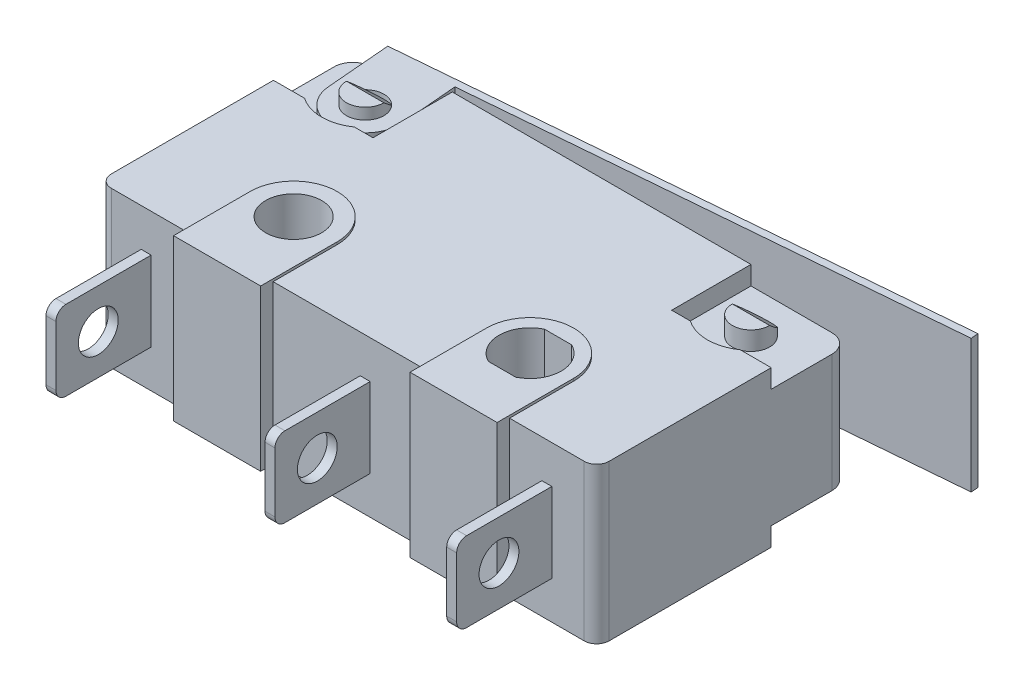
SolidWorks part; units mm, degrees
ref_plane "Front Plane" through (0, 0, 0) normal (0, 0, 1) x (1, 0, 0)
ref_plane "Top Plane" through (0, 0, 0) normal (0, 1, 0) x (1, 0, 0)
ref_plane "Right Plane" through (0, 0, 0) normal (1, 0, 0) x (0, 0, -1)
sketch "Sketch1" plane through (0, 0, 0) normal (0, 1, 0) x (1, 0, 0)
  line L1 (-10, -5.1) -> (10, -5.1)
  line L2 (-10, -5.1) -> (-10, 5.1)
  line L3 (-10, 5.1) -> (10, 5.1)
  line L4 (10, -5.1) -> (10, 5.1)
  line L5 (-10, -5.1) -> (10, 5.1) construction
  line L6 (-10, 5.1) -> (10, -5.1) construction
  point P0 (0, 0)
  dimension "D1" = 20
  dimension "D2" = 10.2
extrude "Boss-Extrude1" add sketch "Sketch1" along normal blind 6.25
fillet "Fillet1" radius 0.75 2 edges at (10, 3.125, -5.1) (-10, 3.125, -5.1)
fillet "Fillet2" radius 0.5 2 edges at (10, 3.125, 5.1) (-10, 3.125, 5.1)
sketch "Sketch2" plane through (0, 6.25, 0) normal (0, 1, 0) x (1, 0, 0)
  line L0 (5.2949, -1.4) -> (4.2051, -1.4)
  line L1 (4.2051, -3.65) -> (5.2949, -3.65)
  line L2 (4.75, -2.525) -> (4.75, -1.4) construction
  line L3 (4.75, -2.525) -> (4.75, -3.65) construction
  line L4 (0, -5.1) -> (0, -2.525) construction
  line L5 (-9.5, -5.1) -> (9.5, -5.1) construction
  line L6 (0, -2.525) -> (4.75, -2.525) construction
  line L7 (0, -2.525) -> (-4.75, -2.525) construction
  line L8 (-4.75, -1.4) -> (-4.75, 5.1) construction
  line L9 (9.25, 5.1) -> (-9.25, 5.1) construction
  line L10 (-4.75, -3.65) -> (-4.75, -5.1) construction
  circle A0 centre (-4.75, -2.525) radius 1.125
  arc A1 (4.2051, -1.4) -> (4.2051, -3.65) centre (4.75, -2.525) ccw
  arc A2 (5.2949, -3.65) -> (5.2949, -1.4) centre (4.75, -2.525) ccw
  dimension "D1" = 2.5
  dimension "D5" = 2.25
  dimension "D2" = 2.25
  dimension "D3" = 9.5
  dimension "D4" = 6.5
extrude "Cut-Extrude1" cut sketch "Sketch2" against normal through all
sketch "Sketch3" plane through (0, 6.25, 0) normal (0, 1, 0) x (1, 0, 0)
  line L0 (-6.5, -5.1) -> (-6.5, -2.525)
  line L1 (-9.5, -5.1) -> (9.5, -5.1) construction
  line L2 (-3, -2.525) -> (-3, -5.1)
  line L3 (-3, -5.1) -> (-3, -5.6)
  line L4 (-3, -5.6) -> (-6.5, -5.6)
  line L5 (-6.5, -5.6) -> (-6.5, -5.1)
  line L6 (0, -5.1) -> (0, 0) construction
  line L7 (6.5, -5.6) -> (6.5, -5.1)
  line L8 (3, -5.6) -> (6.5, -5.6)
  line L9 (3, -5.1) -> (3, -5.6)
  line L10 (3, -2.525) -> (3, -5.1)
  line L11 (6.5, -5.1) -> (6.5, -2.525)
  line L12 (4.2051, -3.65) -> (5.2949, -3.65) construction
  line L13 (5.2949, -1.4) -> (4.2051, -1.4) construction
  line L14 (4.2051, -3.65) -> (5.2949, -3.65)
  line L15 (5.2949, -1.4) -> (4.2051, -1.4)
  arc A0 (-3, -2.525) -> (-6.5, -2.525) centre (-4.75, -2.525) ccw
  circle A1 centre (-4.75, -2.525) radius 1.125 construction
  arc A2 (3, -2.525) -> (6.5, -2.525) centre (4.75, -2.525) cw
  arc A3 (5.2949, -3.65) -> (5.2949, -1.4) centre (4.75, -2.525) ccw construction
  arc A4 (4.2051, -1.4) -> (4.2051, -3.65) centre (4.75, -2.525) ccw construction
  arc A5 (5.2949, -3.65) -> (5.2949, -1.4) centre (4.75, -2.525) ccw
  arc A6 (4.2051, -1.4) -> (4.2051, -3.65) centre (4.75, -2.525) ccw
  circle A7 centre (-4.75, -2.525) radius 1.125
  dimension "D1" = 3.5
  dimension "D2" = 0.5
extrude "Boss-Extrude2" add sketch "Sketch3" against normal offset from surface (6.45 mm away) 0.1 from offset 0.1 up to face at (-4.75, 0, 3.65) offset beyond the face yes
sketch "Sketch4" plane through (0, 6.25, 0) normal (0, 1, 0) x (1, 0, 0)
  line L0 (9.25, 5.1) -> (-9.25, 5.1) construction
  line L1 (-10, 4.35) -> (-10, -4.6) construction
  line L2 (-6, 5.1) -> (-9.25, 5.1)
  line L3 (-10, 4.35) -> (-10, 1.9139)
  line L4 (-6, 5.1) -> (-6, 1.9139)
  line L5 (-6, 1.9139) -> (-6.75, 1.9139)
  line L6 (-10, 1.9139) -> (-8.75, 1.9139)
  line L7 (-8.5, 3.35) -> (-10, 3.35) construction
  line L8 (-7, 3.35) -> (-6, 3.35) construction
  line L9 (-7.75, 2.6) -> (-7.75, 1.6) construction
  line L10 (-7.75, 4.1) -> (-7.75, 5.1) construction
  line L11 (0, 5.1) -> (0, 0) construction
  line L12 (6, 1.9139) -> (6.75, 1.9139)
  line L13 (10, 1.9139) -> (8.75, 1.9139)
  line L14 (10, 4.35) -> (10, 1.9139)
  line L15 (6, 5.1) -> (9.25, 5.1)
  line L16 (6, 5.1) -> (6, 1.9139)
  arc A0 (-9.25, 5.1) -> (-10, 4.35) centre (-9.25, 4.35) ccw construction
  arc A1 (-9.25, 5.1) -> (-10, 4.35) centre (-9.25, 4.35) ccw
  circle A2 centre (-7.75, 3.35) radius 0.75
  arc A3 (-8.75, 1.9139) -> (-6.75, 1.9139) centre (-7.75, 3.35) ccw
  circle A4 centre (7.75, 3.35) radius 0.75
  arc A5 (8.75, 1.9139) -> (6.75, 1.9139) centre (7.75, 3.35) cw
  arc A6 (9.25, 5.1) -> (10, 4.35) centre (9.25, 4.35) cw
  line M19 (10, -4.6) -> (10, 4.35)
  arc M20 (10, 4.35) -> (9.25, 5.1) centre (9.25, 4.35) ccw
  line M21 (9.25, 5.1) -> (-9.25, 5.1)
  arc M22 (-9.25, 5.1) -> (-10, 4.35) centre (-9.25, 4.35) ccw
  line M23 (-10, 4.35) -> (-10, -4.6)
  dimension "D3" = 1.5
  dimension "D1" = 0.75
  dimension "D2" = 1.25
  dimension "D4" = 1
  dimension "D5" = 1
  dimension "D6" = 1
extrude "Cut-Extrude2" cut sketch "Sketch4" against normal blind 0.75 contours L6 A3 L5 L4 A2 M21 M22 M23 | A5 L13 L16 L12 A4 M19 M20 M21 region at (-6.0532, 6.25, -3.5069) region at (7.625, 6.25, -5.0468)
extrude "Cut-Extrude3" cut sketch "Sketch4<4>" along normal blind 0.75 from surface contours L6 A3 L5 L4 A2 M21 M22 M23 | A5 L13 L16 L12 A4 M19 M20 M21 region at (-6.0532, 6.25, -3.5069) region at (7.625, 6.25, -5.0468) starting at face at (0, 0, 1.7123)
sketch "Sketch4<4>" plane through (0, 6.25, 0) normal (0, 1, 0) x (1, 0, 0) same geometry as "Sketch4"
sketch "Sketch5" plane through (-10, 0, 0) normal (-1, 0, 0) x (0, 0, 1)
  line L0 (-2.6, 6.25) -> (-4.1, 6.25) construction
  line L1 (-2.6, 6.25) -> (-4.1, 6.25) construction
  line L3 (-4.1, 6.25) -> (-4.1, 5.6207)
  line L4 (-4.1, 5.6207) -> (-3.35, 6.25)
  line L5 (-3.35, 6.25) -> (-4.1, 6.25)
  dimension "D1" = 40
extrude "Cut-Extrude4" cut sketch "Sketch5" against normal up to surface (4 mm away) up to face at (-6, 5.875, -3.5069)
extrude "Cut-Extrude5" cut sketch "Sketch5<2>" against normal up to surface (20 mm away) from surface up to face at (10, 3.125, -0.8944) starting at face at (6, 5.875, -3.5069)
sketch "Sketch5<2>" plane through (-10, 0, 0) normal (-1, 0, 0) x (0, 0, 1) same geometry as "Sketch5"
ref_plane "Plane1" through (0, 3.125, 0) normal (0, -1, 0) x (-1, 0, 0)
mirror "Mirror2" about plane through (0, 3.125, 0) normal (0, -1, 0) of "Cut-Extrude5", "Cut-Extrude4"
sketch "Sketch6" plane through (0, 3.125, 0) normal (0, -1, 0) x (-1, 0, 0)
  line L0 (-6, 5.1) -> (6, 5.1) construction
  line L1 (2, 5.1) -> (3.6, 5.1)
  line L2 (3.6, 5.1) -> (3.6, 5.3)
  line L3 (2, 5.1) -> (2, 5.3)
  line L4 (2.8, 6.1) -> (2.8, 5.1) construction
  line L5 (-10, 1.9139) -> (-10, 4.35) construction
  arc A0 (3.6, 5.3) -> (2, 5.3) centre (2.8, 5.3) ccw
  dimension "D1" = 1.6
  dimension "D2" = 1
  dimension "D3" = 12
extrude "Boss-Extrude4" add sketch "Sketch6" along normal mid plane 3 separate body
sketch "Sketch7" plane through (0, 0.75, 0) normal (0, -1, 0) x (1, 0, 0)
  line L0 (5.477, -6.8044) -> (-6.5763, -5.7828)
  line L1 (-6.5763, -5.7828) -> (-6.3799, -3.4661)
  line L2 (-9.3418, -5.8495) -> (5.2344, -7.0849)
  line L3 (-7.75, -3.35) -> (-7.9717, -5.9656) construction
  line L4 (-7.75, -3.35) -> (-7.6339, -1.9799) construction
  line L5 (-9.3418, -5.8495) -> (-9.1201, -3.2339)
  line L6 (5.2344, -7.0849) -> (12.5192, -7.7023)
  line L7 (12.5445, -7.4034) -> (12.5192, -7.7023)
  line L8 (5.477, -6.8044) -> (12.5445, -7.4034)
  arc A0 (-6.3799, -3.4661) -> (-9.1201, -3.2339) centre (-7.75, -3.35) ccw
  arc A2 (-3.6, -5.3) -> (-2, -5.3) centre (-2.8, -5.3) ccw construction
  arc A3 (-3.6, -5.3) -> (-2, -5.3) centre (-2.8, -5.3) ccw construction
  arc A4 (-7, -3.35) -> (-8.5, -3.35) centre (-7.75, -3.35) ccw construction
  arc A5 (-7, -3.35) -> (-8.5, -3.35) centre (-7.75, -3.35) ccw
  arc A6 (-8.5, -3.35) -> (-7, -3.35) centre (-7.75, -3.35) ccw construction
  arc A7 (-8.5, -3.35) -> (-7, -3.35) centre (-7.75, -3.35) ccw
  dimension "D1" = 2.75
  dimension "D2" = 4
  dimension "D3" = 0.3
extrude "Boss-Extrude5" add sketch "Sketch7" against normal offset from surface (5.35 mm away) 0.3 from offset 0.3 separate body up to face at (-7.75, 5.5, -2.6) offset beyond the face yes
sketch "Sketch10" plane through (0, 3.125, 0) normal (0, -1, 0) x (-1, 0, 0)
  line L0 (-6.5, -5.1) -> (-9.5, -5.1) construction
  line L1 (3, -5.1) -> (-3, -5.1) construction
  line L2 (9.5, -5.1) -> (6.5, -5.1) construction
  line L3 (-7.8, -5.1) -> (-8.2, -5.1)
  line L4 (-0.5, -5.1) -> (-0.9, -5.1)
  line L5 (8.3, -5.1) -> (7.9, -5.1)
  line L6 (8.1, -5.1) -> (8.1, -8.925) construction
  line L7 (-0.7, -5.1) -> (-0.7, -8.925) construction
  line L8 (-8, -5.1) -> (-8, -8.925) construction
  line L9 (7.9, -5.1) -> (7.9, -8.925)
  line L10 (-0.9, -5.1) -> (-0.9, -8.925)
  line L11 (-8.2, -5.1) -> (-8.2, -8.925)
  line L12 (8.3, -5.1) -> (8.3, -8.925)
  line L13 (-0.5, -5.1) -> (-0.5, -8.925)
  line L14 (-7.8, -5.1) -> (-7.8, -8.925)
  line L15 (4.75, -2.525) -> (4.75, -5.6) construction
  line L16 (6.5, -5.6) -> (3, -5.6) construction
  line L17 (8.3, -8.925) -> (7.9, -8.925)
  line L18 (-0.5, -8.925) -> (-0.9, -8.925)
  line L19 (-7.8, -8.925) -> (-8.2, -8.925)
  dimension "D3" = 6.4
  dimension "D4" = 1.9
  dimension "D5" = 8.8
  dimension "D6" = 7.3
  dimension "D1" = 0.2
  dimension "D2" = 0.2
extrude "Boss-Extrude6" add sketch "Sketch10" along normal mid plane 3.2 separate body
sketch "Sketch11" plane through (-8.3, 0, 0) normal (-1, 0, 0) x (0, 0, 1)
  line L0 (8.025, 3.125) -> (8.925, 3.125) construction
  line L2 (8.925, 1.525) -> (8.925, 4.725) construction
  line L4 (8.925, 1.525) -> (5.1, 1.525) construction
  line L5 (8.925, 4.725) -> (8.925, 4.325)
  line L6 (8.925, 1.525) -> (8.525, 1.525)
  line L7 (8.925, 1.525) -> (8.925, 1.925)
  line L8 (8.925, 4.725) -> (8.525, 4.725)
  circle A0 centre (7.225, 3.125) radius 0.8
  arc A1 (8.525, 1.525) -> (8.925, 1.925) centre (8.525, 1.925) ccw
  arc A2 (8.525, 4.725) -> (8.925, 4.325) centre (8.525, 4.325) cw
  dimension "D1" = 1.6
  dimension "D3" = 0.8
  dimension "D2" = 0.9
extrude "Cut-Extrude8" cut sketch "Sketch11" against normal through all
